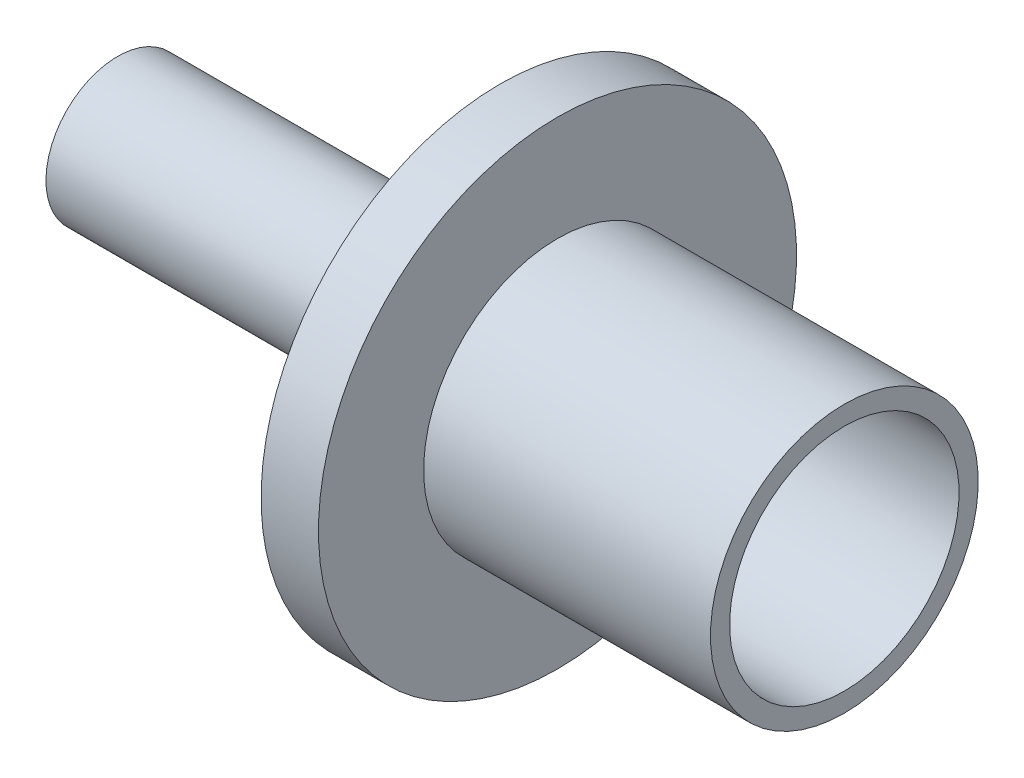
SolidWorks part; units mm, degrees
ref_plane "Front Plane" through (0, 0, 0) normal (0, 0, 1) x (1, 0, 0)
ref_plane "Top Plane" through (0, 0, 0) normal (0, 1, 0) x (1, 0, 0)
ref_plane "Right Plane" through (0, 0, 0) normal (1, 0, 0) x (0, 0, -1)
sketch "Sketch1" plane through (0, 0, 0) normal (0, 0, 1) x (1, 0, 0)
  line L0 (-64.9001, 0) -> (64.9001, 0) construction
  line L1 (-6, 25) -> (-6, 7.5)
  line L2 (-3, 10) -> (0, 10)
  line L3 (0, 10) -> (0, 12)
  line L4 (0, 12) -> (30, 12)
  line L5 (30, 12) -> (30, 14)
  line L6 (30, 14) -> (0, 14)
  line L7 (0, 14) -> (0, 25)
  line L8 (0, 25) -> (-6, 25)
  line L9 (-3, 10) -> (-3, 6.5)
  line L10 (-3, 6.5) -> (-46, 6.5)
  line L11 (-46, 6.5) -> (-46, 7.5)
  line L12 (-46, 7.5) -> (-6, 7.5)
  line L13 (-3, 10) -> (-3, 25) construction
  line L14 (-6, 10) -> (0, 10) construction
  point P3 (0, 0)
  point P6 (-3, 25)
  dimension "D1" = 24
  dimension "D2" = 28
  dimension "D3" = 20
  dimension "D4" = 50
  dimension "D5" = 6
  dimension "D6" = 30
  dimension "D7" = 15
  dimension "D8" = 40
  dimension "D9" = 13
revolve "Revolve1" add sketch "Sketch1" angle 360 about L0
